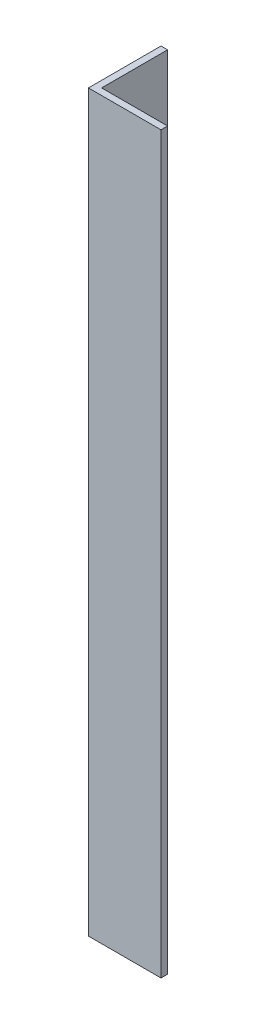
SolidWorks part; units mm, degrees
ref_plane "Спереди" through (0, 0, 0) normal (0, 0, 1) x (1, 0, 0)
ref_plane "Сверху" through (0, 0, 0) normal (0, 1, 0) x (1, 0, 0)
ref_plane "Справа" through (0, 0, 0) normal (1, 0, 0) x (0, 0, -1)
sketch "Эскиз1" plane through (0, 0, 0) normal (0, 1, 0) x (1, 0, 0)
  line L0 (0, 33) -> (0, 0)
  line L1 (0, 0) -> (33, 0)
extrude "Вытянуть-Тонкостенный1" add sketch "Эскиз1" along normal blind 334 thin thin type one direction reverse wall 3
